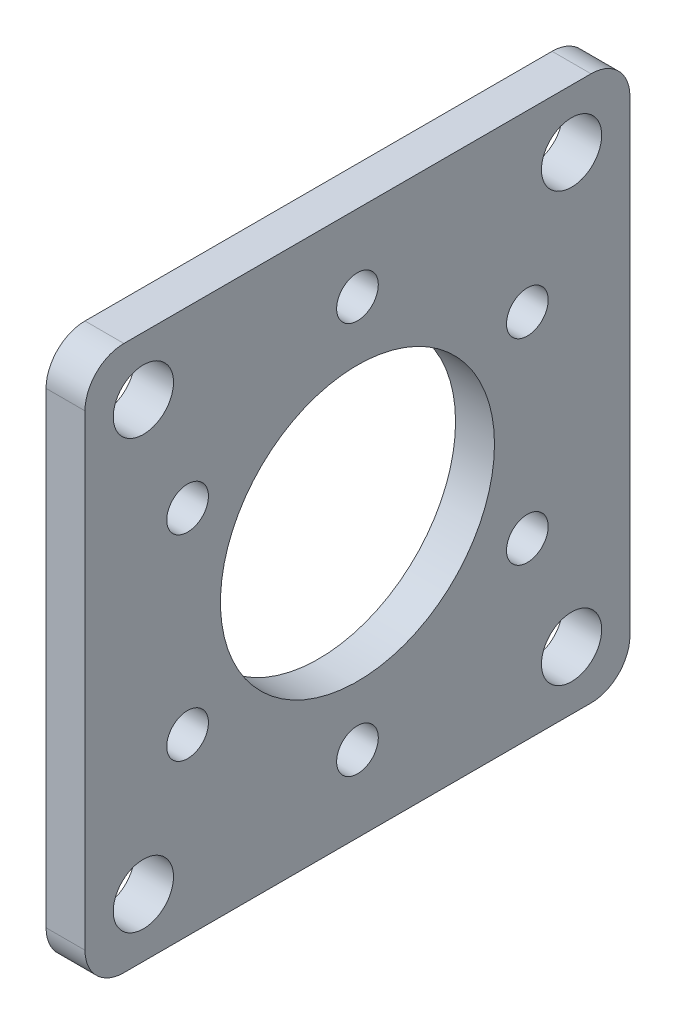
SolidWorks part; units mm, degrees
material "6061-T6 (SS)"
ref_plane "Front" through (0, 0, 0) normal (0, 0, 1) x (1, 0, 0)
ref_plane "Top" through (0, 0, 0) normal (0, 1, 0) x (1, 0, 0)
ref_plane "Right" through (0, 0, 0) normal (1, 0, 0) x (0, 0, -1)
sketch "Sketch1" plane through (0, 0, 0) normal (1, 0, 0) x (0, 0, -1)
  line L1 (22.225, -22.225) -> (-22.225, -22.225)
  line L2 (22.225, -22.225) -> (22.225, 22.225)
  line L3 (22.225, 22.225) -> (-22.225, 22.225)
  line L4 (-22.225, -22.225) -> (-22.225, 22.225)
  line L5 (22.225, -22.225) -> (-22.225, 22.225) construction
  line L6 (22.225, 22.225) -> (-22.225, -22.225) construction
  circle A0 centre (0, 0) radius 11.176
  dimension "D1" = 22.352
  dimension "D2" = 44.45
  dimension "D3" = 44.45
extrude "Boss-Extrude1" add sketch "Sketch1" along normal blind 3.175
sketch "Sketch4" plane through (3.175, 0, 0) normal (1, 0, 0) x (0, 0, -1)
  line L1 (22.225, 22.225) -> (-22.225, 22.225) construction
  line L2 (-22.225, 22.225) -> (-22.225, -22.225) construction
  line L3 (22.225, -22.225) -> (22.225, 22.225) construction
  line L4 (-22.225, -22.225) -> (22.225, -22.225) construction
  point P0 (-17.4625, 17.4625)
  point P2 (17.4625, 17.4625)
  point P4 (17.4625, -17.4625)
  point P6 (-17.4625, -17.4625)
  dimension "D1" = 4.7625
  dimension "D2" = 4.7625
  dimension "D3" = 4.7625
  dimension "D4" = 4.7625
hole_wizard "#10 (0.1935) Diameter Hole1" positions "Sketch4" profile "Sketch3" hole size "#10" standard "ANSI Inch" end condition up to next
sketch "Sketch3" plane through (3.175, 17.4625, 17.4625) normal (0, 1, 0) x (0, 0, -1)
  line L0 (0, 0) -> (0, 3.175)
  line L1 (0, 3.175) -> (2.4574, 3.175)
  line L2 (2.4574, 3.175) -> (2.4574, 0)
  line L5 (2.4574, 0) -> (0, 0)
  line L11 (0, -6.35) -> (0, 107.95) construction
  dimension "Thru Hole Dia." = 4.9149
  dimension "Thru Hole Depth" = 3.175
sketch "Sketch7" plane through (3.175, 0, 0) normal (1, 0, 0) x (0, 0, -1)
  circle A0 centre (0, 0) radius 16 construction
  point P5 (0, 16)
  point P11 (13.8564, 8)
  point P12 (13.8564, -8)
  point P13 (0, -16)
  point P14 (-13.8564, -8)
  point P15 (-13.8564, 8)
  dimension "D2" = 32
  dimension "D1" = 6
hole_wizard "M3 Clearance Hole1" positions "Sketch7" profile "Sketch6" hole size "M3" standard "ANSI Metric" end condition up to next
sketch "Sketch6" plane through (3.175, 8, 13.8564) normal (0, 1, 0) x (0, 0, -1)
  line L0 (0, 0) -> (0, 3.175)
  line L1 (0, 3.175) -> (1.7, 3.175)
  line L2 (1.7, 3.175) -> (1.7, 0)
  line L5 (1.7, 0) -> (0, 0)
  line L11 (0, -6.35) -> (0, 107.95) construction
  dimension "Thru Hole Dia." = 3.4
  dimension "Thru Hole Depth" = 3.175
fillet "Fillet1" radius 3.175 4 edges at (1.5875, 22.225, 22.225) (1.5875, 22.225, -22.225) (1.5875, -22.225, -22.225) (1.5875, -22.225, 22.225)
